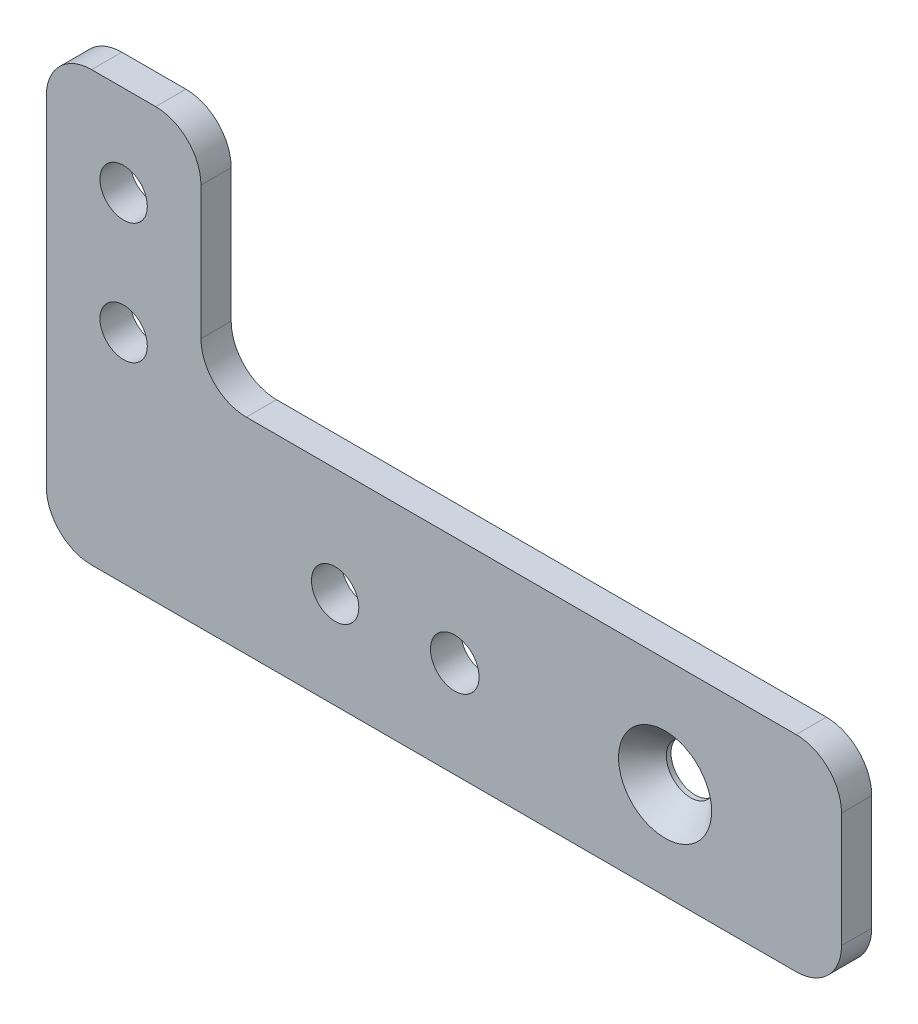
SolidWorks part; units mm, degrees
material "6061-T6 (SS)"
ref_plane "Front Plane" through (0, 0, 0) normal (0, 0, 1) x (1, 0, 0)
ref_plane "Top Plane" through (0, 0, 0) normal (0, 1, 0) x (1, 0, 0)
ref_plane "Right Plane" through (0, 0, 0) normal (1, 0, 0) x (0, 0, -1)
sketch "Sketch1" plane through (0, 0, 0) normal (0, 0, 1) x (1, 0, 0)
  line L0 (-21.59, 23.8125) -> (-37.846, 23.8125) construction
  line L1 (-45.72, -23.8125) -> (45.72, -23.8125)
  line L2 (-45.72, -23.8125) -> (-45.72, 23.8125)
  line L3 (-45.72, 23.8125) -> (45.72, 23.8125)
  line L4 (45.72, -23.8125) -> (45.72, 23.8125)
  line L5 (-45.72, -23.8125) -> (45.72, 23.8125) construction
  line L6 (-45.72, 23.8125) -> (45.72, -23.8125) construction
  line L7 (45.72, 23.8125) -> (-21.59, 23.8125)
  line L8 (45.72, 23.8125) -> (45.72, 0.3175)
  line L9 (45.72, 0.3175) -> (-21.59, 0.3175)
  line L10 (-21.59, 23.8125) -> (-21.59, 0.3175)
  line L11 (-45.72, -23.8125) -> (-37.846, -23.8125)
  line L12 (-45.72, -23.8125) -> (-45.72, 23.8125)
  line L13 (-45.72, 23.8125) -> (-37.846, 23.8125)
  line L14 (-37.846, -23.8125) -> (-37.846, 23.8125)
  line L15 (-37.846, -23.8125) -> (45.72, -23.8125)
  line L16 (-37.846, -23.8125) -> (-37.846, -21.2725)
  line L17 (-37.846, -21.2725) -> (45.72, -21.2725)
  line L18 (45.72, -23.8125) -> (45.72, -21.2725)
  line L19 (-21.59, 23.8125) -> (-37.846, 23.8125) construction
  line L20 (-29.718, 23.8125) -> (-29.718, -21.2725) construction
  circle A0 centre (-29.718, -11.1125) radius 2.4892
  circle A1 centre (-29.718, 1.5875) radius 2.4892
  circle A2 centre (-29.718, 14.2875) radius 2.4892
  circle A4 centre (-7.493, -11.1125) radius 2.4892
  circle A5 centre (5.08, -11.1125) radius 2.5527
  circle A7 centre (27.178, -11.1125) radius 2.5527
  point P0 (0, 0)
  point P31 (-10.795, -11.1125)
  dimension "D7" = 30.353
  dimension "D18" = 5.1054
  dimension "D19" = 4.9784
  dimension "D13" = 22.098
  dimension "D1" = 91.44
  dimension "D2" = 9.525
  dimension "D3" = 24.13
  dimension "D4" = 24.13
  dimension "D5" = 7.874
  dimension "D6" = 47.625
  dimension "D9" = 12.7
  dimension "D10" = 12.7
  dimension "D11" = 12.7
  dimension "D15" = 12.573
  dimension "D16" = 2.54
extrude "Boss-Extrude1" add sketch "Sketch1" along normal blind 3.175 contours L14 L17 L4 L9 L10 L3 A5 A4 A2 A1 A0 | A0 region at (-1.4639, -6.6351, 0) region at (-29.718, -11.1125, 0)
fillet "Fillet1" radius 4.7625 6 edges at (-37.846, 23.8125, 1.5875) (-21.59, 23.8125, 1.5875) (-21.59, 0.3175, 1.5875) (45.72, 0.3175, 1.5875) (45.72, -21.2725, 1.5875) (-37.846, -21.2725, 1.5875)
hole_wizard "CSK for #10 Flat Head Machine Screw1" positions "Sketch3" profile "Sketch4" countersink size "#10" standard "ANSI Inch"
sketch "Sketch3" plane through (0, 0, 3.175) normal (0, 0, 1) x (1, 0, 0)
  point P0 (27.178, -11.1125)
sketch "Sketch4" plane through (27.178, -11.1125, 3.175) normal (1, 0, 0) x (0, -1, 0)
  line L0 (0, 0) -> (0, 20.5838)
  line L1 (0, 20.5838) -> (2.5527, 19.05)
  line L2 (2.5527, 19.05) -> (2.5527, 2.6882)
  line L3 (2.5527, 2.6882) -> (4.8895, 0)
  line L5 (4.8895, 0) -> (0, 0)
  line L6 (-2.5527, 2.6882) -> (-4.8895, 0) construction
  line L10 (0, 20.5838) -> (-2.5527, 19.05) construction
  line L11 (0, -6.35) -> (0, 107.95) construction
  dimension "Hole Dia." = 5.1054
  dimension "Hole Depth" = 19.05
  dimension "Near C'Sink Dia." = 9.779
  dimension "Near C'Sink Angle" = 82
  dimension "Drill Angle" = 118
